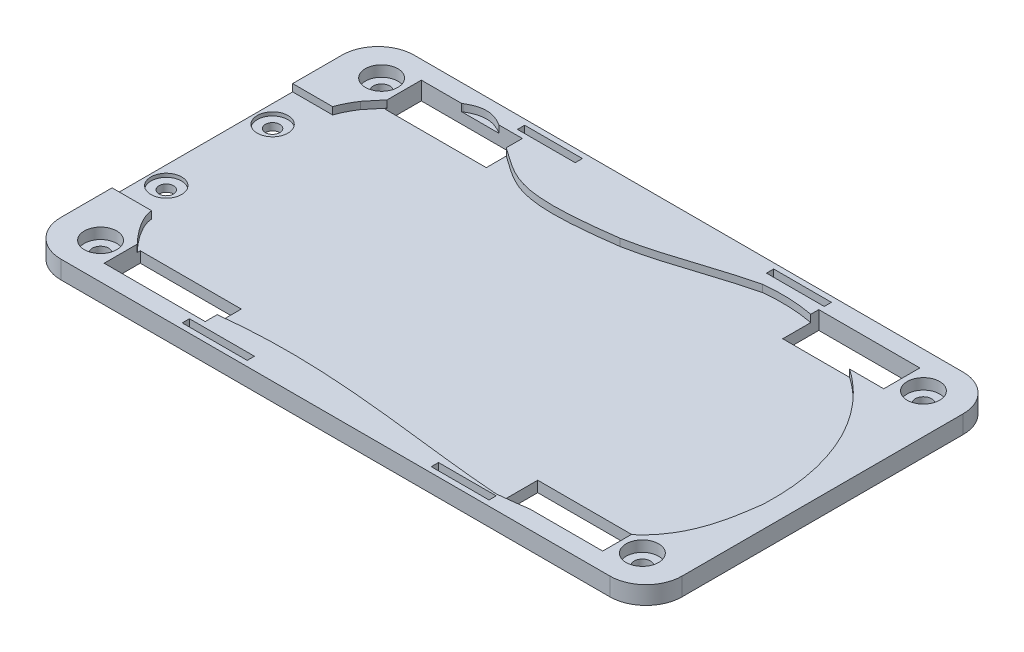
SolidWorks part; units mm, degrees
ref_plane "Front Plane" through (0, 0, 0) normal (0, 0, 1) x (1, 0, 0)
ref_plane "Top Plane" through (0, 0, 0) normal (0, 1, 0) x (1, 0, 0)
ref_plane "Right Plane" through (0, 0, 0) normal (1, 0, 0) x (0, 0, -1)
sketch "Sketch1" plane through (0, 0, 0) normal (0, 1, 0) x (1, 0, 0)
  line L1 (-78.1571, 35.933) -> (-78.1571, -14.1122)
  line L2 (78.9797, 0.0343) -> (-78.1571, 0.0343) construction
  line L3 (-77.1571, 35.7646) -> (-77.1571, -14.1122)
  line L4 (78.9797, -0.9657) -> (-78.1571, -0.9657)
  arc A1 (37.8695, -35.2975) -> (39.5975, -35.2134) centre (38.2635, -25.6055) ccw
  arc A2 (37.9263, -34.299) -> (39.4753, -34.2207) centre (38.2635, -25.6055) ccw
  spline S0 degree 1 poles (-77.1571, -14.1122) (-56.919, -31.9168) knots 0 0 1 1 construction
  spline S1 degree 1 poles (-56.919, -31.9168) (37.9263, -34.299) knots 0 0 1 1 construction
  spline S2 degree 1 poles (39.4753, -34.2207) (77.9849, 0.1477) knots 0 0 1 1 construction
  spline S3 degree 1 poles (77.9849, 0.1477) (25.0602, 52.8732) knots 0 0 1 1 construction
  spline S4 degree 1 poles (25.0602, 52.8732) (-5.6593, 44.1904) knots 0 0 1 1 construction
  spline S5 degree 1 poles (-5.6593, 44.1904) (-43.9853, 50.6886) knots 0 0 1 1 construction
  spline S6 degree 1 poles (-43.9853, 50.6886) (-59.7702, 54.7238) knots 0 0 1 1 construction
  spline S7 degree 1 poles (-59.7702, 54.7238) (-74.5158, 41.0521) knots 0 0 1 1 construction
  spline S8 degree 1 poles (-74.5158, 41.0521) (-77.1571, 35.7646) knots 0 0 1 1 construction
  spline S9 degree 3 poles (-77.1571, -14.1122) (-77.1565, -14.3701) (-77.1092, -14.8732) (-76.8359, -15.9559) (-76.1879, -17.5008) (-75.044, -19.4183) (-73.152, -22.0092) (-70.3495, -25.0822) (-66.8736, -28.0972) (-63.6864, -30.2141) (-61.0019, -31.4062) (-58.8274, -31.848) (-57.5718, -31.8794) (-56.919, -31.9168) knots 0.000484 0.000484 0.000484 0.000484 0.031521 0.062558 0.124632 0.186706 0.248781 0.372929 0.497077 0.621225 0.745373 0.869521 0.993669 0.993669 0.993669 0.993669
  spline S10 degree 3 poles (-56.919, -31.9168) (-56.6769, -31.8873) (-56.2021, -31.8274) (-55.1791, -31.687) (-53.8294, -31.4877) (-52.0759, -31.2184) (-49.5744, -30.8354) (-46.1465, -30.3372) (-41.5825, -29.7813) (-36.5976, -29.3261) (-29.4274, -28.913) (-19.5571, -28.8468) (-6.4839, -29.5875) (5.2448, -30.7865) (15.023, -31.9295) (22.521, -32.809) (30.1538, -33.642) (35.3408, -34.1075) (37.9263, -34.299) knots 0.000538 0.000538 0.000538 0.000538 0.016152 0.031766 0.062993 0.094221 0.125449 0.187904 0.250359 0.312815 0.37527 0.50018 0.625091 0.750001 0.812457 0.874912 0.937367 0.999822 0.999822 0.999822 0.999822
  spline S11 degree 3 poles (39.4753, -34.2207) (41.0079, -34.0574) (44.09, -33.7147) (50.0835, -32.8429) (57.0969, -31.1859) (64.2184, -27.8839) (69.7763, -23.1857) (73.0497, -18.2789) (74.9177, -14.0269) (75.9805, -10.7732) (76.7509, -7.5724) (77.1995, -5.064) (77.4798, -3.2279) (77.6607, -1.9649) (77.8261, -0.8108) (77.9301, -0.1834) (77.9849, 0.1477) knots -0.000309 -0.000309 -0.000309 -0.000309 0.063093 0.126495 0.253299 0.380104 0.506908 0.633712 0.697114 0.760516 0.823918 0.88732 0.919021 0.950722 0.982423 1.014124 1.014124 1.014124 1.014124
  spline S12 degree 3 poles (77.9849, 0.1477) (78.0286, 1.2633) (78.0637, 3.5224) (77.9426, 6.757) (77.6596, 9.9047) (77.0733, 13.9671) (75.9626, 18.7836) (73.4433, 25.9357) (69.0206, 33.8098) (62.0495, 41.4932) (53.7895, 47.3444) (44.6121, 51.2947) (34.9036, 53.2804) (28.3113, 53.2357) (25.0602, 52.8732) knots 0.000169 0.000169 0.000169 0.000169 0.031414 0.062658 0.093902 0.125147 0.187635 0.250124 0.375101 0.500079 0.625056 0.750034 0.875011 0.999988 0.999988 0.999988 0.999988
  spline S13 degree 3 poles (25.0602, 52.8732) (19.8954, 51.6294) (12.3224, 49.1317) (2.1607, 45.9713) (-3.0371, 44.6913) (-5.6593, 44.1904) knots 0.000659 0.000659 0.000659 0.000659 0.498067 0.746772 0.995476 0.995476 0.995476 0.995476
  spline S14 degree 3 poles (-5.6593, 44.1904) (-6.6879, 44.0461) (-8.7287, 43.7719) (-12.9633, 43.2668) (-18.1826, 42.7952) (-23.9015, 42.6322) (-28.8306, 42.9899) (-32.9666, 43.9514) (-35.9177, 45.2914) (-38.1959, 46.6779) (-39.9392, 47.8658) (-41.507, 48.9798) (-42.8638, 49.9292) (-43.6163, 50.4405) (-43.9853, 50.6886) knots -0.000196 -0.000196 -0.000196 -0.000196 0.062587 0.12537 0.250936 0.376501 0.502067 0.627632 0.753198 0.815981 0.878764 0.941546 0.972938 1.004329 1.004329 1.004329 1.004329
  spline S15 degree 3 poles (-43.9853, 50.6886) (-44.2445, 50.8673) (-44.7682, 51.2325) (-45.7507, 51.9331) (-46.8912, 52.7591) (-48.146, 53.6496) (-49.6971, 54.6811) (-51.4608, 55.6487) (-53.4077, 56.2593) (-55.2517, 56.3574) (-56.711, 56.0808) (-57.7948, 55.7138) (-58.5465, 55.3915) (-59.2299, 55.0428) (-59.5837, 54.8359) (-59.7702, 54.7238) knots -0.002497 -0.002497 -0.002497 -0.002497 0.029066 0.060629 0.123754 0.18688 0.250006 0.376257 0.502509 0.62876 0.755012 0.818137 0.881263 0.944389 1.007515 1.007515 1.007515 1.007515
  spline S16 degree 3 poles (-78.1571, -14.1122) (-78.1559, -14.7524) (-77.9173, -15.9777) (-77.0678, -17.9828) (-75.8538, -20.0098) (-73.8827, -22.6985) (-70.9901, -25.8584) (-67.4096, -28.9504) (-64.0991, -31.1349) (-61.2379, -32.3904) (-59.243, -32.7789) (-57.8421, -32.8756) (-57.2118, -32.9007) (-56.8882, -32.9203) knots 0.000409 0.000409 0.000409 0.000409 0.062843 0.125276 0.18771 0.250143 0.375011 0.499878 0.624745 0.749612 0.874479 0.936913 0.999346 0.999346 0.999346 0.999346
  spline S17 degree 3 poles (-56.8882, -32.9203) (-56.6427, -32.8908) (-56.1603, -32.8306) (-55.1309, -32.6904) (-53.7754, -32.491) (-52.0233, -32.2221) (-49.5292, -31.8398) (-46.1189, -31.3427) (-41.5829, -30.7872) (-36.6286, -30.3313) (-29.4997, -29.9158) (-19.6749, -29.8441) (-6.6369, -30.5782) (5.0856, -31.7749) (14.8757, -32.919) (22.3927, -33.8009) (30.0532, -34.6371) (35.2704, -35.1052) (37.8695, -35.2975) knots -0.001373 -0.001373 -0.001373 -0.001373 0.014273 0.029919 0.06121 0.092502 0.123794 0.186377 0.24896 0.311543 0.374127 0.499293 0.62446 0.749626 0.81221 0.874793 0.937376 0.99996 0.99996 0.99996 0.99996
  spline S18 degree 3 poles (39.5975, -35.2134) (41.1398, -35.049) (44.2356, -34.7045) (50.3018, -33.8209) (57.4502, -32.1301) (64.7991, -28.7164) (70.5782, -23.8111) (73.9656, -18.7006) (75.8832, -14.3057) (76.9672, -10.962) (77.7479, -7.6914) (78.1997, -5.145) (78.4804, -3.2966) (78.6613, -2.0308) (78.824, -0.9009) (78.9276, -0.2806) (78.9816, 0.0458) knots -0.000086 -0.000086 -0.000086 -0.000086 0.063428 0.126941 0.253967 0.380993 0.50802 0.635046 0.698559 0.762072 0.825585 0.889098 0.920855 0.952612 0.984368 1.016125 1.016125 1.016125 1.016125
  spline S19 degree 3 poles (78.9816, 0.0458) (79.0271, 1.1797) (79.0647, 3.4739) (78.9444, 6.7697) (78.6587, 9.9749) (78.0642, 14.1169) (76.9341, 19.0326) (74.3646, 26.3398) (69.8439, 34.3944) (62.712, 42.2543) (54.2626, 48.2351) (44.8799, 52.2671) (34.9529, 54.2886) (28.2109, 54.2351) (24.8869, 53.8601) knots -0.000407 -0.000407 -0.000407 -0.000407 0.03088 0.062166 0.093453 0.12474 0.187314 0.249888 0.375035 0.500183 0.62533 0.750478 0.875625 1.000773 1.000773 1.000773 1.000773
  spline S20 degree 3 poles (24.8869, 53.8601) (22.2839, 53.2349) (17.1223, 51.77) (6.9788, 48.4835) (-0.6206, 46.1711) (-5.8226, 45.1772) knots -0.001281 -0.001281 -0.001281 -0.001281 0.247714 0.49671 0.9947 0.9947 0.9947 0.9947
  spline S21 degree 3 poles (-5.8226, 45.1772) (-6.8463, 45.0337) (-8.8779, 44.761) (-13.0882, 44.2593) (-18.2643, 43.7927) (-23.9018, 43.6338) (-28.7026, 43.9859) (-32.6523, 44.9085) (-35.4477, 46.177) (-37.6484, 47.5152) (-39.3619, 48.6824) (-40.9248, 49.793) (-42.292, 50.7496) (-43.0505, 51.2651) (-43.4225, 51.5151) knots 0.000305 0.000305 0.000305 0.000305 0.063048 0.125791 0.251276 0.376761 0.502247 0.627732 0.753218 0.815961 0.878703 0.941446 0.972817 1.004189 1.004189 1.004189 1.004189
  spline S22 degree 3 poles (-43.4225, 51.5151) (-43.6786, 51.6918) (-44.1958, 52.0526) (-45.1684, 52.7462) (-46.308, 53.5714) (-47.577, 54.4721) (-49.1727, 55.5335) (-51.0441, 56.5648) (-53.2147, 57.2519) (-55.3195, 57.3652) (-56.9568, 57.0533) (-58.1477, 56.6506) (-58.9689, 56.2985) (-59.5708, 55.992) (-60.0059, 55.7483) (-60.1862, 55.6406) (-60.2803, 55.5839) knots -0.002294 -0.002294 -0.002294 -0.002294 0.029245 0.060783 0.12386 0.186936 0.250013 0.376167 0.50232 0.628473 0.754627 0.817704 0.88078 0.943857 0.975396 1.006934 1.006934 1.006934 1.006934
  spline S23 degree 3 poles (-60.2803, 55.5839) (-60.715, 55.3297) (-61.582, 54.801) (-63.2222, 53.7187) (-65.9105, 51.7373) (-69.2431, 48.741) (-72.0244, 45.6929) (-73.7392, 43.6279) (-74.6657, 42.4756) (-75.1049, 41.9202) (-75.3265, 41.639) knots 0.000427 0.000427 0.000427 0.000427 0.063268 0.126109 0.251792 0.503158 0.754524 0.880206 0.943048 1.005889 1.005889 1.005889 1.005889
  spline S24 degree 3 poles (-59.7702, 54.7238) (-60.1936, 54.4761) (-61.0386, 53.9612) (-62.6368, 52.9072) (-65.2587, 50.9763) (-68.5171, 48.0498) (-71.2443, 45.0657) (-73.1899, 42.7247) (-74.0698, 41.6179) (-74.5158, 41.0521) knots 0.000174 0.000174 0.000174 0.000174 0.062881 0.125589 0.251004 0.501833 0.752662 0.878077 1.003492 1.003492 1.003492 1.003492
  spline S25 degree 3 poles (-74.5158, 41.0521) (-75.0658, 40.2217) (-76.0765, 38.4779) (-76.8336, 36.6875) (-77.1571, 35.7646) knots 0.499549 0.499549 0.499549 0.499549 0.499766 0.499983 0.499983 0.499983 0.499983
  spline S26 degree 3 poles (-75.3265, 41.639) (-75.92, 40.746) (-77.0064, 38.8701) (-77.815, 36.9314) (-78.1571, 35.933) knots 0.499546 0.499546 0.499546 0.499546 0.49977 0.499995 0.499995 0.499995 0.499995
  point P0 (0.4631, 0.0343)
  dimension "D1" = 1
sketch "Sketch6" plane through (0, 0, 0) normal (0, 1, 0) x (1, 0, 0)
  line L0 (-78.1571, 35.933) -> (-78.1571, -14.1122) construction
  line L1 (73.9816, 59.5839) -> (-78.1571, 59.5839)
  line L2 (83.9816, 49.5839) -> (83.9816, -28.2975)
  line L3 (73.9816, -38.2975) -> (-78.1571, -38.2975)
  line L4 (-88.1571, 49.5839) -> (-88.1571, -28.2975)
  arc A0 (-78.1571, -38.2975) -> (-88.1571, -28.2975) centre (-78.1571, -28.2975) cw
  arc A1 (-88.1571, 49.5839) -> (-78.1571, 59.5839) centre (-78.1571, 49.5839) cw
  arc A2 (73.9816, 59.5839) -> (83.9816, 49.5839) centre (73.9816, 49.5839) cw
  arc A3 (83.9816, -28.2975) -> (73.9816, -38.2975) centre (73.9816, -28.2975) cw
  dimension "D5" = 10
  dimension "D1" = 5
  dimension "D2" = 10
  dimension "D3" = 3
  dimension "D4" = 4
extrude "Boss-Extrude2" add sketch "Sketch6" along normal blind 6.5
extrude "Cut-Extrude1" cut sketch "Sketch1" along normal blind 2.5 contours A2 S11 L4 L3 S9 S10 | S24 S25 L3 L4 S11 S12 S13 S14 S15 region at (0.1139, 0, 15.5782) region at (-2.2602, 0, -23.2786)
sketch "Sketch7" plane through (0, 0, 0) normal (0, -1, 0) x (1, 0, 0)
  line L1 (-76.2189, 14.1122) -> (-91.3452, 14.1122)
  line L2 (-76.2189, 14.1122) -> (-76.2189, -35.933)
  line L3 (-76.2189, -35.933) -> (-91.3452, -35.933)
  line L4 (-91.3452, 14.1122) -> (-91.3452, -35.933)
extrude "Cut-Extrude2" cut sketch "Sketch7" against normal up to surface (2.5 mm away) contours L2 L1 L4 L3 up to face at (-19.4492, 2.5, -12.7234)
sketch "Sketch8" plane through (0, 6.5, 0) normal (0, 1, 0) x (1, 0, 0)
  line L0 (83.9816, 10.6432) -> (-88.1571, 10.6432) construction
  line L1 (83.9816, -28.2975) -> (83.9816, 49.5839) construction
  line L2 (-88.1571, 49.5839) -> (-88.1571, -28.2975) construction
  line L3 (-2.0877, 59.5839) -> (-2.0877, -38.2975) construction
  line L4 (73.9816, 59.5839) -> (-78.1571, 59.5839) construction
  line L5 (-78.1571, -38.2975) -> (73.9816, -38.2975) construction
  line L7 (78.9816, 54.5839) -> (38.9816, 54.5839)
  line L8 (78.9816, 54.5839) -> (78.9816, 44.5839)
  line L9 (78.9816, 44.5839) -> (38.9816, 44.5839)
  line L10 (38.9816, 54.5839) -> (38.9816, 44.5839)
  line L22 (38.9816, 49.5839) -> (78.9816, 49.5839) construction
  line L23 (66.9816, 54.5839) -> (66.9816, 44.5839)
  circle A1 centre (72.9816, 49.5839) radius 3.5
  dimension "D6" = 7
  dimension "D1" = 10
  dimension "D2" = 40
  dimension "D3" = 5
  dimension "D4" = 5
  dimension "D5" = 6
  dimension "D7" = 6
sketch "Sketch9" plane through (0, 0, 0) normal (0, -1, 0) x (1, 0, 0)
  circle A0 centre (72.9816, -49.5839) radius 4.5
  dimension "D1" = 9
extrude "Cut-Extrude5" cut sketch "Sketch9" against normal blind 3.5
sketch "Sketch10" plane through (0, 3.5, 0) normal (0, -1, 0) x (1, 0, 0)
  circle A0 centre (72.9816, -49.5839) radius 2.25
  dimension "D1" = 4.5
extrude "Cut-Extrude6" cut sketch "Sketch10" against normal blind 21
extrude "Cut-Extrude8" cut sketch "Sketch8" against normal blind 42 contours L23 L7 L10 L9 region at (52.9816, 6.5, -49.5839)
extrude "Cut-Extrude9" cut sketch "Sketch8<3>" against normal blind 1 contours L7 L23 L9 L8 A1 region at (78.8254, 6.5, -49.5839)
sketch "Sketch8<3>" plane through (0, 6.5, 0) normal (0, 1, 0) x (1, 0, 0) same geometry as "Sketch8"
sketch "Sketch12" plane through (0, 6.5, 0) normal (0, 1, 0) x (1, 0, 0)
  line L0 (-88.1571, 10.6432) -> (83.9816, 10.6432) construction
  line L1 (-88.1571, 49.5839) -> (-88.1571, -28.2975) construction
  line L2 (83.9816, -28.2975) -> (83.9816, 49.5839) construction
  line L3 (-2.0877, 59.5839) -> (-2.0877, -36.8461) construction
  line L4 (73.9816, 59.5839) -> (-78.1571, 59.5839) construction
ref_plane "Plane1" through (0, 0, -10.6432) normal (0, 0, 1) x (1, 0, 0)
ref_plane "Plane2" through (-2.0877, 0, 0) normal (-1, 0, 0) x (0, 0, 1)
mirror "Mirror1" about plane through (0, 0, -10.6432) normal (0, 0, 1) of "Cut-Extrude5", "Cut-Extrude6", "Cut-Extrude8", "Cut-Extrude9"
mirror "Mirror2" about plane through (-2.0877, 0, 0) normal (-1, 0, 0) of "Mirror1", "Cut-Extrude9", "Cut-Extrude8", "Cut-Extrude6", "Cut-Extrude5"
sketch "Sketch13" plane through (0, 6.5, 0) normal (0, 1, 0) x (1, 0, 0)
  line L0 (-83.1571, 44.5839) -> (-43.1571, 44.5839) construction
  line L1 (58.9816, 39.5839) -> (-63.1571, 39.5839)
  line L2 (58.9816, 39.5839) -> (58.9816, -18.2975)
  line L3 (58.9816, -18.2975) -> (-63.1571, -18.2975)
  line L4 (-63.1571, 39.5839) -> (-63.1571, -18.2975)
  line L5 (58.9816, 39.5839) -> (-63.1571, -18.2975) construction
  line L6 (58.9816, -18.2975) -> (-63.1571, 39.5839) construction
  line L7 (-83.1571, -23.2975) -> (-43.1571, -23.2975) construction
  line L8 (83.9816, -28.2975) -> (83.9816, 49.5839) construction
  line L9 (-88.1571, 49.5839) -> (-88.1571, -28.2975) construction
  point P0 (-2.0877, 10.6432)
  dimension "D1" = 5
  dimension "D2" = 5
  dimension "D3" = 25
  dimension "D4" = 25
extrude "Cut-Extrude10" cut sketch "Sketch13" against normal blind 1
sketch "Sketch14" plane through (0, 5.5, 0) normal (0, 1, 0) x (1, 0, 0)
  line L0 (-63.1571, 10.6432) -> (58.9816, 10.6432) construction
  line L1 (-63.1571, 39.5839) -> (-63.1571, -18.2975) construction
  line L2 (58.9816, -18.2975) -> (58.9816, 39.5839) construction
  line L3 (-63.1571, -9.3568) -> (58.9816, -9.3568) construction
  line L4 (-63.1571, 10.6432) -> (58.9816, 10.6432) construction
  line L5 (-63.1571, 30.6432) -> (58.9816, 30.6432) construction
  circle A1 centre (-12.0877, 10.6432) radius 2.5
  circle A2 centre (-32.0877, 10.6432) radius 2.5
  circle A3 centre (-52.0877, 10.6432) radius 2.5
  circle A4 centre (-12.0877, 10.6432) radius 2.5
  circle A5 centre (-32.0877, 10.6432) radius 2.5
  circle A6 centre (7.9123, 10.6432) radius 2.5
  circle A7 centre (-12.0877, 10.6432) radius 2.5
  circle A8 centre (27.9123, 10.6432) radius 2.5
  circle A9 centre (7.9123, 10.6432) radius 2.5
  circle A10 centre (7.9123, 10.6432) radius 2.5
  circle A11 centre (27.9123, 10.6432) radius 2.5
  circle A12 centre (47.9123, 10.6432) radius 2.5
  circle A13 centre (-12.0877, -9.3568) radius 2.5
  circle A14 centre (-32.0877, -9.3568) radius 2.5
  circle A15 centre (-52.0877, -9.3568) radius 2.5
  circle A16 centre (-12.0877, -9.3568) radius 2.5
  circle A17 centre (-32.0877, -9.3568) radius 2.5
  circle A18 centre (7.9123, -9.3568) radius 2.5
  circle A19 centre (-12.0877, -9.3568) radius 2.5
  circle A20 centre (27.9123, -9.3568) radius 2.5
  circle A21 centre (7.9123, -9.3568) radius 2.5
  circle A22 centre (7.9123, -9.3568) radius 2.5
  circle A23 centre (27.9123, -9.3568) radius 2.5
  circle A24 centre (47.9123, -9.3568) radius 2.5
  circle A25 centre (-12.0877, 10.6432) radius 2.5
  circle A26 centre (-32.0877, 10.6432) radius 2.5
  circle A27 centre (-52.0877, 10.6432) radius 2.5
  circle A28 centre (-12.0877, 10.6432) radius 2.5
  circle A29 centre (-32.0877, 10.6432) radius 2.5
  circle A30 centre (7.9123, 10.6432) radius 2.5
  circle A31 centre (-12.0877, 10.6432) radius 2.5
  circle A32 centre (27.9123, 10.6432) radius 2.5
  circle A33 centre (7.9123, 10.6432) radius 2.5
  circle A34 centre (7.9123, 10.6432) radius 2.5
  circle A35 centre (27.9123, 10.6432) radius 2.5
  circle A36 centre (47.9123, 10.6432) radius 2.5
  circle A37 centre (-12.0877, 30.6432) radius 2.5
  circle A38 centre (-32.0877, 30.6432) radius 2.5
  circle A39 centre (-52.0877, 30.6432) radius 2.5
  circle A40 centre (-12.0877, 30.6432) radius 2.5
  circle A41 centre (-32.0877, 30.6432) radius 2.5
  circle A42 centre (7.9123, 30.6432) radius 2.5
  circle A43 centre (-12.0877, 30.6432) radius 2.5
  circle A44 centre (27.9123, 30.6432) radius 2.5
  circle A45 centre (7.9123, 30.6432) radius 2.5
  circle A46 centre (7.9123, 30.6432) radius 2.5
  circle A47 centre (27.9123, 30.6432) radius 2.5
  circle A48 centre (47.9123, 30.6432) radius 2.5
  point P8 (-2.0877, 10.6432)
  point P37 (-2.0877, -9.3568)
  point P64 (-2.0877, 10.6432)
  point P91 (-2.0877, 30.6432)
  dimension "D2" = 5
  dimension "D1" = 10
  dimension "D3" = 3
  dimension "D4" = 4
  dimension "D5" = 2
  dimension "D6" = 2
extrude "Cut-Extrude11" cut sketch "Sketch14" against normal blind 57 contours A39 | A42 | A44 | A48 | A12 | A6 | A1 | A2 | A3 | A24 | A20 | A18 | A13 | A14 | A15 | A38 | A37 | A8 region at (-12.0877, 5.5, -10.6432) region at (-32.0877, 5.5, -10.6432) region at (-52.0877, 5.5, -10.6432) region at (7.9123, 5.5, -10.6432) region at (47.9123, 5.5, -10.6432) region at (-12.0877, 5.5, 9.3568) region at (-32.0877, 5.5, 9.3568) region at (-52.0877, 5.5, 9.3568) region at (7.9123, 5.5, 9.3568) region at (27.9123, 5.5, 9.3568) region at (47.9123, 5.5, 9.3568) region at (-52.0877, 5.5, -30.6432) region at (7.9123, 5.5, -30.6432) region at (27.9123, 5.5, -30.6432) region at (47.9123, 5.5, -30.6432)
sketch "Sketch16" plane through (0, 0, 0) normal (0, -1, 0) x (1, 0, 0)
  line L0 (78.9816, -0.5458) -> (78.9816, -79.1994) construction
  line L1 (22.9816, -56.0839) -> (-37.6427, -56.0839) construction
  line L2 (73.9816, -59.5839) -> (-78.1571, -59.5839) construction
  line L3 (38.9816, -54.3238) -> (38.9816, 38.2975) construction
  line L4 (38.9816, -59.5839) -> (38.9816, -54.3238) construction
  line L5 (38.9816, -56.0839) -> (22.9816, -56.0839)
  line L6 (38.9816, -56.0839) -> (38.9816, -58.0839)
  line L7 (38.9816, -58.0839) -> (22.9816, -58.0839)
  line L8 (22.9816, -56.0839) -> (22.9816, -58.0839)
  line L9 (-78.1571, 38.2975) -> (73.9816, 38.2975) construction
  line L10 (22.9816, -56.0839) -> (22.9816, 38.2975) construction
  line L12 (38.9816, 36.7975) -> (22.9816, 36.7975)
  line L13 (38.9816, 36.7975) -> (38.9816, 34.7975)
  line L14 (38.9816, 34.7975) -> (22.9816, 34.7975)
  line L15 (22.9816, 36.7975) -> (22.9816, 34.7975)
  line L16 (22.9816, 34.7975) -> (-46.0184, 34.7975) construction
  line L17 (-30.0184, -56.0839) -> (-46.0184, -56.0839)
  line L18 (-30.0184, -56.0839) -> (-30.0184, -58.0839)
  line L19 (-30.0184, -58.0839) -> (-46.0184, -58.0839)
  line L20 (-46.0184, -56.0839) -> (-46.0184, -58.0839)
  line L22 (-28.0184, 34.7975) -> (-46.0184, 34.7975)
  line L23 (-28.0184, 34.7975) -> (-28.0184, 36.7975)
  line L24 (-28.0184, 36.7975) -> (-46.0184, 36.7975)
  line L25 (-46.0184, 34.7975) -> (-46.0184, 36.7975)
  dimension "D1" = 40
  dimension "D2" = 16
  dimension "D3" = 1.5
  dimension "D4" = 2
  dimension "D5" = 2
  dimension "D6" = 1.5
  dimension "D7" = 125
  dimension "D8" = 16
  dimension "D9" = 2
  dimension "D10" = 18
  dimension "D11" = 2
extrude "Cut-Extrude12" cut sketch "Sketch16" against normal blind 57
sketch "Sketch17" plane through (0, 5.5, 0) normal (0, 1, 0) x (1, 0, 0)
  line L1 (-99.5963, 69.0247) -> (98.4238, 69.0247)
  line L2 (-99.5963, 69.0247) -> (-99.5963, -53.2143)
  line L3 (-99.5963, -53.2143) -> (98.4238, -53.2143)
  line L4 (98.4238, 69.0247) -> (98.4238, -53.2143)
extrude "Cut-Extrude14" cut sketch "Sketch17" along normal blind 48.5
sketch "Sketch23" plane through (0, 2.5, 0) normal (0, -1, 0) x (1, 0, 0)
  line L0 (-88.1571, -10.9104) -> (-64.7808, -10.9104) construction
  line L1 (-88.1571, -35.933) -> (-88.1571, 14.1122) construction
  circle A0 centre (-83.1571, 4.0896) radius 2
  circle A1 centre (-83.1571, 4.0896) radius 4.25
  dimension "D1" = 4
  dimension "D4" = 8.5
  dimension "D2" = 15
  dimension "D3" = 5
extrude "Cut-Extrude15" cut sketch "Sketch23" against normal blind 48.5 contours A0
extrude "Cut-Extrude16" cut sketch "Sketch23<3>" against normal blind 1
sketch "Sketch23<3>" plane through (0, 2.5, 0) normal (0, -1, 0) x (1, 0, 0) same geometry as "Sketch23"
mirror "Mirror4" about plane through (0, 0, -10.6432) normal (0, 0, 1) of "Cut-Extrude16", "Cut-Extrude15"
sketch "Sketch24" plane through (0, 5.5, 0) normal (0, 1, 0) x (1, 0, 0)
  circle A0 centre (-77.1571, 49.5839) radius 3.25
  circle A1 centre (-77.1571, 49.5839) radius 2.25
  circle A2 centre (72.9816, 49.5839) radius 2.25
  circle A3 centre (72.9816, 49.5839) radius 3.25
  circle A4 centre (72.9816, -28.2975) radius 2.25
  circle A5 centre (-77.1571, -28.2975) radius 2.25
  circle A6 centre (-77.1571, -28.2975) radius 3.25
  circle A7 centre (72.9816, -28.2975) radius 3.25
  dimension "D1" = 6.5
  dimension "D2" = 6.5
  dimension "D3" = 6.5
  dimension "D4" = 6.5
extrude "Boss-Extrude3" add sketch "Sketch24" along normal blind 3
ref_plane "Plane3" through (0, 0, 0) normal (0, -1, 0) x (-1, 0, 0)
mirror "Mirror5" about plane through (0, 0, 0) normal (0, -1, 0) of "Boss-Extrude3", "Mirror4", "Cut-Extrude16", "Cut-Extrude15", "Cut-Extrude14", "Cut-Extrude12", "Cut-Extrude10", "Mirror2", "Mirror1", "Cut-Extrude9", "Cut-Extrude8", "Cut-Extrude6", "Cut-Extrude5", "Cut-Extrude2", "Cut-Extrude1", "Boss-Extrude2", "Cut-Extrude11"
sketch "Sketch25" plane through (0, 5.5, 0) normal (0, 1, 0) x (1, 0, 0)
  line L1 (-109.2871, 73.7066) -> (111.0455, 73.7066)
  line L2 (-109.2871, 73.7066) -> (-109.2871, -75.7235)
  line L3 (-109.2871, -75.7235) -> (111.0455, -75.7235)
  line L4 (111.0455, 73.7066) -> (111.0455, -75.7235)
extrude "Cut-Extrude18" cut sketch "Sketch25" against normal up to surface (5.5 mm away) and the other way blind 10 contours L2 L1 L4 L3 up to plane "Plane3"
ref_plane "Plane4" through (-77.0974, 0, 0) normal (-1, 0, 0) x (0, 0, 1)
ref_plane "Plane6" through (0, 0, -35.933) normal (0, 0, 1) x (1, 0, 0)
sketch "Sketch26" plane through (0, 0, 0) normal (0, 1, 0) x (1, 0, 0)
  line L1 (-104.6518, 69.0589) -> (106.0904, 69.0589)
  line L2 (-104.6518, 69.0589) -> (-104.6518, -52.1551)
  line L3 (-104.6518, -52.1551) -> (106.0904, -52.1551)
  line L4 (106.0904, 69.0589) -> (106.0904, -52.1551)
extrude "Cut-Extrude19" cut sketch "Sketch26" against normal blind 0.5
sketch "Sketch27" plane through (0, -2.5, 0) normal (0, 1, 0) x (1, 0, 0)
  line L1 (-59.9586, 37.3138) -> (59.6605, 37.3138)
  line L2 (-59.9586, 37.3138) -> (-59.9586, -15.8502)
  line L3 (-59.9586, -15.8502) -> (59.6605, -15.8502)
  line L4 (59.6605, 37.3138) -> (59.6605, -15.8502)
extrude "Boss-Extrude4" add sketch "Sketch27" against normal up to surface (3 mm away) up to face at (72.9816, -5.5, 25.0475)
sketch "Sketch28" plane through (0, -2.5, 0) normal (0, 1, 0) x (1, 0, 0)
  line L0 (73.9816, 59.5839) -> (-78.1571, 59.5839) construction
  line L6 (-88.1571, -14.1122) -> (-88.1571, 35.933) construction
  line L9 (-78.1571, -38.2975) -> (73.9816, -38.2975) construction
  line L10 (83.9816, -28.2975) -> (83.9816, 49.5839) construction
  line L11 (43.3816, 59.5839) -> (45.6816, -38.2975) construction
  line L12 (43.3816, 59.5839) -> (43.3816, -38.2975) construction
  line L13 (72.9816, -28.2975) -> (-77.1571, 49.5839) construction
  line L14 (72.9816, 49.5839) -> (-77.1571, -28.2975) construction
  point P0 (-26.0571, 3.8839)
  point P3 (43.3816, 59.5839)
  point P4 (45.6816, -38.2975)
  point P22 (-2.0877, 10.6432)
  dimension "D1" = 55.7
  dimension "D2" = 62.1
  dimension "D3" = 40.6
  dimension "D4" = 38.3
  dimension "D5" = 1.346
  dimension "D6" = 23.9694
  dimension "D7" = 6.7593
